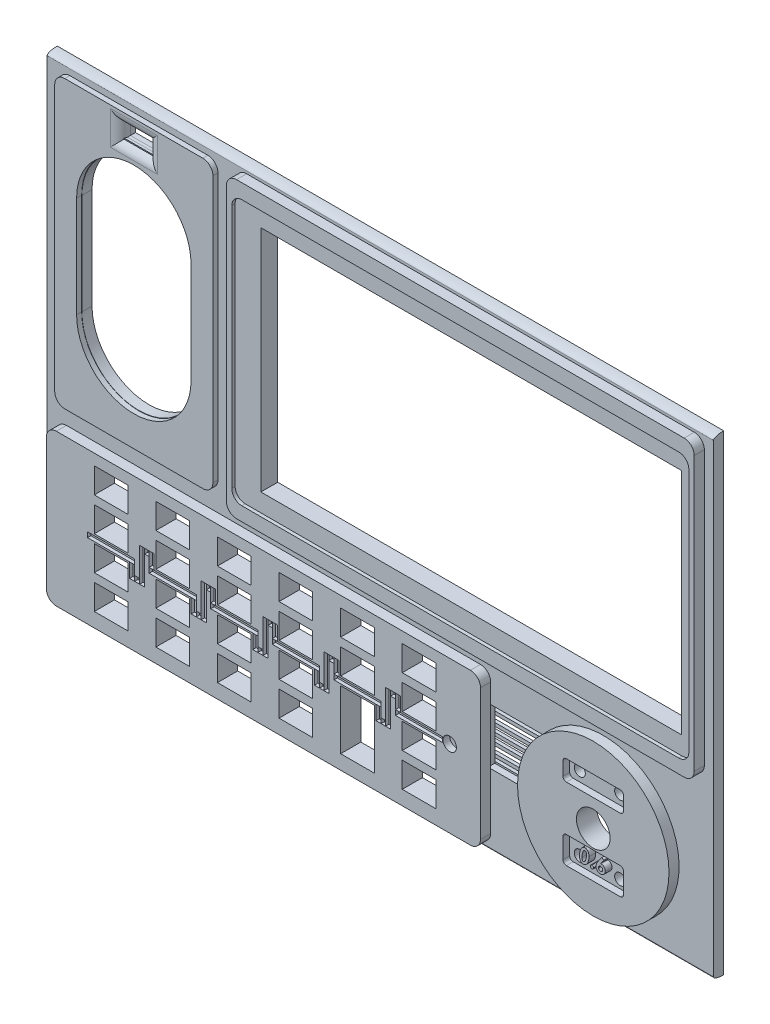
SolidWorks part; units mm, degrees
ref_plane "Front Plane" through (0, 0, 0) normal (0, 0, 1) x (1, 0, 0)
ref_plane "Top Plane" through (0, 0, 0) normal (0, 1, 0) x (1, 0, 0)
ref_plane "Right Plane" through (0, 0, 0) normal (1, 0, 0) x (0, 0, -1)
sketch "Sketch1" plane through (0, 0, 0) normal (0, 0, 1) x (1, 0, 0)
  line L1 (99, -70) -> (-99, -70)
  line L2 (99, -70) -> (99, 70)
  line L3 (99, 70) -> (-99, 70)
  line L4 (-99, -70) -> (-99, 70)
  line L5 (99, -70) -> (-99, 70) construction
  line L6 (99, 70) -> (-99, -70) construction
  point P0 (0, 0)
  dimension "D1" = 198
  dimension "D2" = 140
extrude "main_body" add sketch "Sketch1" along normal blind 3
fillet "long_corners" radius 3 2 edges at (0, 70, 3) (0, -70, 3) second distance 1 first distance on face at (0, 70, 1.5) first distance on face at (0, -70, 1.5)
sketch "Sketch2" plane through (0, 0, 3) normal (0, 0, 1) x (1, 0, 0)
  line L0 (-99, 24.75) -> (99, 24.75) construction
  line L1 (-99, 69) -> (-99, -69) construction
  line L2 (99, -69) -> (99, 69) construction
  line L3 (99, 69) -> (-99, 69) construction
  line L4 (-48.25, -17.75) -> (-95.25, -17.75)
  line L5 (-48.25, -17.75) -> (-48.25, 67.25)
  line L6 (-48.25, 67.25) -> (-95.25, 67.25)
  line L7 (-95.25, -17.75) -> (-95.25, 67.25)
  line L8 (-48.25, -17.75) -> (-95.25, 67.25) construction
  line L9 (-48.25, 67.25) -> (-95.25, -17.75) construction
  point P6 (-71.75, 24.75)
  dimension "D1" = 85
  dimension "D2" = 47
  dimension "D3" = 27.25
  dimension "D4" = 44.25
extrude "speaker" add sketch "Sketch2" along normal blind 1.5
fillet "speaker_corners" radius 3 4 edges at (-95.25, 67.25, 3.75) (-95.25, -17.75, 3.75) (-48.25, -17.75, 3.75) (-48.25, 67.25, 3.75)
sketch "Sketch19" plane through (0, 0, 4.5) normal (0, 0, 1) x (1, 0, 0)
  line L0 (-71.75, 67.25) -> (-71.75, -17.75) construction
  line L1 (-51.25, 67.25) -> (-92.25, 67.25) construction
  line L2 (-92.25, -17.75) -> (-51.25, -17.75) construction
  line L3 (-71.75, 8.25) -> (-71.75, 38.25) construction
  line L4 (-95.25, 64.25) -> (-95.25, -14.75) construction
  line L5 (-95.25, 24.75) -> (-48.25, 24.75) construction
  line L6 (-48.25, -14.75) -> (-48.25, 64.25) construction
  line L7 (-88.75, 8.25) -> (-88.75, 38.25)
  line L8 (-54.75, 8.25) -> (-54.75, 38.25)
  arc A0 (-88.75, 8.25) -> (-54.75, 8.25) centre (-71.75, 8.25) ccw
  arc A1 (-54.75, 38.25) -> (-88.75, 38.25) centre (-71.75, 38.25) ccw
  point P14 (-71.75, 23.25)
  point P19 (-71.75, -8.75)
  point P20 (-71.75, 55.25)
  dimension "D2" = 64
  dimension "D1" = 34
  dimension "D3" = 12
extrude "speaker_cut" cut sketch "Sketch19" against normal through all
sketch "Sketch21" plane through (0, 0, 0) normal (0, 0, -1) x (-1, 0, 0)
  line L0 (71.75, -8.75) -> (71.75, 55.25) construction
  line L2 (54.75, 8.25) -> (54.75, 38.25) construction
  line L3 (54.75, 23.25) -> (88.75, 23.25) construction
  line L4 (88.75, 38.25) -> (88.75, 8.25) construction
  line L5 (50.25, 59.25) -> (93.25, 59.25)
  line L6 (50.25, 59.25) -> (50.25, -12.75)
  line L7 (50.25, -12.75) -> (93.25, -12.75)
  line L8 (93.25, 59.25) -> (93.25, -12.75)
  line L9 (50.25, 59.25) -> (93.25, -12.75) construction
  line L10 (50.25, -12.75) -> (93.25, 59.25) construction
  arc A0 (54.75, 8.25) -> (88.75, 8.25) centre (71.75, 8.25) ccw construction
  arc A1 (88.75, 38.25) -> (54.75, 38.25) centre (71.75, 38.25) ccw construction
  point P14 (71.75, 23.25)
  dimension "D1" = 43
  dimension "D2" = 72
extrude "speaker_slot" cut sketch "Sketch21" against normal blind 3
sketch "Sketch36" plane through (0, 0, 3) normal (0, 0, -1) x (-1, 0, 0)
  line L0 (50.25, 23.25) -> (93.25, 23.25) construction
  line L1 (50.25, 59.25) -> (50.25, -12.75) construction
  line L2 (71.75, 8.2639) -> (71.75, 38.2361) construction
  line L3 (71.75, 8.2639) -> (71.75, 38.2361) construction
  line L4 (93.25, -12.75) -> (93.25, 59.25) construction
  line L5 (50.25, 59.25) -> (50.25, -12.75) construction
  line L6 (54.8316, 8.2639) -> (54.8316, 38.2361)
  line L9 (88.6684, 8.2639) -> (88.6684, 38.2361)
  line L10 (54.25, 8.2639) -> (54.25, 38.2361)
  line L11 (89.25, 8.2639) -> (89.25, 38.2361)
  line L12 (93.25, 59.25) -> (50.25, 59.25) construction
  line L13 (71.75, 59.25) -> (71.75, -12.75) construction
  line L14 (50.25, -12.75) -> (93.25, -12.75) construction
  line L23 (50.25, 57.25) -> (93.25, 57.25)
  line L25 (50.25, 57.25) -> (50.25, 56.75)
  line L26 (93.25, -0.25) -> (87.75, -0.25)
  line L27 (50.25, 56.75) -> (93.25, 56.75)
  line L28 (93.25, 57.25) -> (93.25, 56.75)
  line L37 (93.25, -12.75) -> (93.25, 59.25) construction
  line L38 (93.25, -0.25) -> (93.25, 0.25)
  line L39 (93.25, 0.25) -> (87.75, 0.25)
  line L48 (93.25, -10.75) -> (50.25, -10.75)
  line L49 (93.25, -10.75) -> (93.25, -10.25)
  line L50 (93.25, -10.25) -> (50.25, -10.25)
  line L51 (50.25, -10.75) -> (50.25, -10.25)
  line L52 (93.25, 46.75) -> (87.75, 46.75)
  line L53 (93.25, 46.75) -> (93.25, 46.25)
  line L54 (93.25, 46.25) -> (87.75, 46.25)
  line L55 (87.75, 46.75) -> (87.75, 46.25)
  line L56 (93.25, 35.25) -> (89.75, 35.25)
  line L57 (93.25, 35.25) -> (93.25, 34.75)
  line L58 (93.25, 34.75) -> (89.75, 34.75)
  line L59 (89.75, 35.25) -> (89.75, 34.75)
  line L60 (93.25, 23.25) -> (89.75, 23.25)
  line L61 (93.25, 23.25) -> (93.25, 23.75)
  line L62 (93.25, 23.75) -> (89.75, 23.75)
  line L63 (89.75, 23.25) -> (89.75, 23.75)
  line L64 (93.25, 10.75) -> (89.75, 10.75)
  line L65 (93.25, 10.75) -> (93.25, 11.25)
  line L66 (93.25, 11.25) -> (89.75, 11.25)
  line L67 (89.75, 10.75) -> (89.75, 11.25)
  line L68 (87.75, -0.25) -> (87.75, 0.25)
  line L69 (93.25, -5.25) -> (83.25, -5.25)
  line L70 (93.25, -5.25) -> (93.25, -5.75)
  line L71 (93.25, -5.75) -> (83.25, -5.75)
  line L72 (83.25, -5.25) -> (83.25, -5.75)
  line L73 (93.25, 52.25) -> (83.25, 52.25)
  line L74 (93.25, 52.25) -> (93.25, 51.75)
  line L75 (93.25, 51.75) -> (83.25, 51.75)
  line L76 (83.25, 52.25) -> (83.25, 51.75)
  line L77 (50.25, 52.25) -> (60.25, 52.25)
  line L78 (50.25, 52.25) -> (50.25, 51.75)
  line L79 (50.25, 51.75) -> (60.25, 51.75)
  line L80 (60.25, 52.25) -> (60.25, 51.75)
  line L81 (50.25, 46.75) -> (55.75, 46.75)
  line L82 (50.25, 46.75) -> (50.25, 46.25)
  line L83 (50.25, 46.25) -> (55.75, 46.25)
  line L84 (55.75, 46.75) -> (55.75, 46.25)
  line L85 (50.25, 35.25) -> (53.75, 35.25)
  line L86 (50.25, 35.25) -> (50.25, 34.75)
  line L87 (50.25, 34.75) -> (53.75, 34.75)
  line L88 (53.75, 35.25) -> (53.75, 34.75)
  line L89 (50.25, 23.25) -> (53.75, 23.25)
  line L90 (50.25, 23.25) -> (50.25, 23.75)
  line L91 (50.25, 23.75) -> (53.75, 23.75)
  line L92 (53.75, 23.25) -> (53.75, 23.75)
  line L93 (50.25, 10.25) -> (53.75, 10.25)
  line L94 (50.25, 10.25) -> (50.25, 10.75)
  line L95 (50.25, 10.75) -> (53.75, 10.75)
  line L96 (53.75, 10.25) -> (53.75, 10.75)
  line L97 (50.25, -0.25) -> (55.75, -0.25)
  line L98 (50.25, -0.25) -> (50.25, 0.25)
  line L99 (50.25, 0.25) -> (55.75, 0.25)
  line L100 (55.75, -0.25) -> (55.75, 0.25)
  line L101 (50.25, -5.25) -> (60.25, -5.25)
  line L102 (50.25, -5.25) -> (50.25, -5.75)
  line L103 (50.25, -5.75) -> (60.25, -5.75)
  line L104 (60.25, -5.25) -> (60.25, -5.75)
  arc A0 (54.25, 8.2639) -> (89.25, 8.2639) centre (71.75, 8.2639) ccw
  arc A1 (89.25, 38.2361) -> (54.25, 38.2361) centre (71.75, 38.2361) ccw
  arc A4 (54.8316, 8.2639) -> (88.6684, 8.2639) centre (71.75, 8.2639) ccw
  arc A5 (88.6684, 38.2361) -> (54.8316, 38.2361) centre (71.75, 38.2361) ccw
  point P6 (71.75, 23.25)
  point P22 (71.75, 23.25)
  point P31 (89.25, 23.25)
  point P32 (71.75, 55.1546)
  point P33 (71.75, -8.6546)
  point P95 (52, 35.25)
  point P96 (55.25, 51.75)
  point P97 (91.5, 10.75)
  dimension "D48" = 0.5816
  dimension "D1" = 33.8368
  dimension "D2" = 35
  dimension "D3" = 63.8091
  dimension "D4" = 0.5
  dimension "D5" = 0.5
  dimension "D6" = 0.5
  dimension "D7" = 0.5
  dimension "D8" = 0.5
  dimension "D9" = 11
  dimension "D10" = 11
  dimension "D11" = 5
  dimension "D12" = 4.5
  dimension "D13" = 10
  dimension "D14" = 5.5
  dimension "D15" = 3.5
  dimension "D16" = 3.5
  dimension "D17" = 0.5
  dimension "D18" = 0.5
  dimension "D19" = 0.5
  dimension "D20" = 0.5
  dimension "D21" = 11
  dimension "D22" = 11
  dimension "D23" = 5
  dimension "D24" = 10
  dimension "D25" = 5.5
  dimension "D26" = 3.5
  dimension "D27" = 3.5
  dimension "D28" = 0.5
  dimension "D29" = 0.5
  dimension "D30" = 0.5
  dimension "D31" = 0.5
  dimension "D32" = 0.5
  dimension "D33" = 0.5
  dimension "D34" = 0.5
  dimension "D35" = 12
  dimension "D36" = 10.5
  dimension "D37" = 5.5
  dimension "D38" = 5
  dimension "D39" = 4.5
  dimension "D40" = 3.5
  dimension "D41" = 10
  dimension "D42" = 4.5
  dimension "D43" = 5
  dimension "D44" = 10
  dimension "D45" = 3.5
  dimension "D46" = 5.5
  dimension "D47" = 10
extrude "speaker_print_support" add sketch "Sketch36" along normal blind 3
sketch "Sketch3" plane through (0, 0, 3) normal (0, 0, 1) x (1, 0, 0)
  line L0 (-99, 24.625) -> (99, 24.625) construction
  line L1 (-99, 69) -> (-99, -69) construction
  line L2 (99, -69) -> (99, 69) construction
  line L4 (-48.25, -14.75) -> (-48.25, 64.25) construction
  line L5 (96.25, -19) -> (-42.75, -19)
  line L6 (96.25, -19) -> (96.25, 68.25)
  line L7 (96.25, 68.25) -> (-42.75, 68.25)
  line L8 (-42.75, -19) -> (-42.75, 68.25)
  line L9 (96.25, -19) -> (-42.75, 68.25) construction
  line L10 (96.25, 68.25) -> (-42.75, -19) construction
  line L11 (99, 70) -> (-99, 70) construction
  point P8 (26.75, 24.625)
  dimension "D1" = 1.75
  dimension "D2" = 87.25
  dimension "D3" = 139
  dimension "D4" = 2.75
  dimension "D5" = 5.5
extrude "lcd" add sketch "Sketch3" along normal blind 3
fillet "lcd_corners" radius 3 4 edges at (96.25, -19, 4.5) (-42.75, -19, 4.5) (96.25, 68.25, 4.5) (-42.75, 68.25, 4.5)
sketch "Sketch9" plane through (0, 0, 6) normal (0, 0, 1) x (1, 0, 0)
  line L0 (-42.75, 24.5) -> (96.25, 24.5) construction
  line L1 (-42.75, 65.25) -> (-42.75, -16) construction
  line L2 (96.25, -16) -> (96.25, 65.25) construction
  line L3 (-39.75, -19) -> (93.25, -19) construction
  line L4 (94.65, -14.875) -> (-41.15, -14.875)
  line L5 (94.65, -14.875) -> (94.65, 63.875)
  line L6 (94.65, 63.875) -> (-41.15, 63.875)
  line L7 (-41.15, -14.875) -> (-41.15, 63.875)
  line L8 (94.65, -14.875) -> (-41.15, 63.875) construction
  line L9 (94.65, 63.875) -> (-41.15, -14.875) construction
  line L10 (93.25, 68.25) -> (-39.75, 68.25) construction
  line L11 (96.25, -16) -> (96.25, 65.25) construction
  point P6 (26.75, 24.5)
  dimension "D1" = 135.8
  dimension "D2" = 78.75
  dimension "D3" = 1.6
  dimension "D4" = 4.125
  dimension "D5" = 4.375
  dimension "D6" = 1.6
extrude "lcd_front" cut sketch "Sketch9" against normal blind 1
fillet "lcd_front_corners" radius 3 4 edges at (94.65, -14.875, 5.5) (94.65, 63.875, 5.5) (-41.15, 63.875, 5.5) (-41.15, -14.875, 5.5)
sketch "Sketch10" plane through (0, 0, 0) normal (0, 0, -1) x (-1, 0, 0)
  line L0 (-94.65, -11.875) -> (-94.65, 60.875) construction
  line L1 (-91.65, 63.875) -> (38.15, 63.875) construction
  line L2 (41.15, 63.875) -> (41.15, -14.875) construction
  line L3 (-94.65, 63.875) -> (41.15, 63.875) construction
  line L4 (33.5, -9.5) -> (-91.5, -9.5)
  line L5 (33.5, -9.5) -> (33.5, 58.5)
  line L6 (33.5, 58.5) -> (-91.5, 58.5)
  line L7 (-91.5, -9.5) -> (-91.5, 58.5)
  line L8 (-91.5, -9.5) -> (33.5, 58.5) construction
  line L9 (-91.5, 58.5) -> (33.5, -9.5) construction
  line L10 (-99, -70) -> (-99, 70) construction
  line L11 (-99, 70) -> (99, 70) construction
  line L13 (38.15, -14.875) -> (-91.65, -14.875) construction
  dimension "D1" = 125
  dimension "D2" = 68
  dimension "D3" = 7.5
  dimension "D4" = 7.65
  dimension "D5" = 11.5
  dimension "D6" = 5.375
  dimension "D7" = 3.15
  dimension "D8" = 5.375
  dimension "D9" = 5.375
extrude "lcd_back" cut sketch "Sketch10" against normal through all
sketch "Sketch4" plane through (0, 0, 3) normal (0, 0, 1) x (1, 0, 0)
  line L0 (-99, -45.75) -> (99, -45.75) construction
  line L1 (-99, 69) -> (-99, -69) construction
  line L2 (99, -69) -> (99, 69) construction
  line L4 (-92.25, -17.75) -> (-51.25, -17.75) construction
  line L5 (32.75, -68.25) -> (-96.25, -68.25)
  line L6 (32.75, -68.25) -> (32.75, -23.25)
  line L7 (32.75, -23.25) -> (-96.25, -23.25)
  line L8 (-96.25, -68.25) -> (-96.25, -23.25)
  line L9 (32.75, -68.25) -> (-96.25, -23.25) construction
  line L10 (32.75, -23.25) -> (-96.25, -68.25) construction
  line L11 (-99, -70) -> (99, -70) construction
  point P8 (-31.75, -45.75)
  dimension "D1" = 1.75
  dimension "D2" = 129
  dimension "D3" = 45
  dimension "D4" = 2.75
  dimension "D5" = 5.5
extrude "keypad" add sketch "Sketch4" along normal blind 3
fillet "keypad_corners" radius 3 4 edges at (-96.25, -68.25, 4.5) (32.75, -68.25, 4.5) (32.75, -23.25, 4.5) (-96.25, -23.25, 4.5)
sketch "Sketch25" plane through (0, 0, 6) normal (0, 0, 1) x (1, 0, 0)
  line L0 (-96.25, -30.25) -> (32.75, -30.25) construction
  line L1 (29.75, -23.25) -> (-93.25, -23.25) construction
  line L2 (-93.25, -68.25) -> (29.75, -68.25) construction
  line L3 (-77, -23.25) -> (-77, -68.25) construction
  line L5 (-35.4, -64) -> (32.75, -64) construction
  line L6 (-96.25, -26.25) -> (-96.25, -65.25) construction
  line L11 (32.75, -65.25) -> (32.75, -26.25) construction
  line L12 (-58.7, -23.25) -> (-58.7, -68.25) construction
  line L13 (-96.25, -40.25) -> (32.75, -40.25) construction
  line L14 (29.75, -23.25) -> (-93.25, -23.25) construction
  line L15 (-40.4, -23.25) -> (-40.4, -68.25) construction
  line L16 (-93.25, -68.25) -> (29.75, -68.25) construction
  line L17 (-72, -34) -> (-82, -34)
  line L18 (-22.1, -23.25) -> (-22.1, -68.25) construction
  line L19 (-96.25, -50.25) -> (32.75, -50.25) construction
  line L20 (-3.8, -23.25) -> (-3.8, -68.25) construction
  line L21 (-72, -34) -> (-72, -26.5)
  line L22 (14.5, -23.25) -> (14.5, -68.25) construction
  line L23 (-96.25, -26.25) -> (-96.25, -65.25) construction
  line L24 (-96.25, -60.25) -> (32.75, -60.25) construction
  line L25 (-72, -26.5) -> (-82, -26.5)
  line L26 (-82, -34) -> (-82, -26.5)
  line L27 (-72, -34) -> (-82, -26.5) construction
  line L28 (-72, -26.5) -> (-82, -34) construction
  line L29 (-72, -44) -> (-82, -44)
  line L30 (-72, -44) -> (-72, -36.5)
  line L31 (-72, -36.5) -> (-82, -36.5)
  line L32 (-82, -44) -> (-82, -36.5)
  line L33 (-72, -44) -> (-82, -36.5) construction
  line L34 (-72, -36.5) -> (-82, -44) construction
  line L35 (-72, -54) -> (-82, -54)
  line L36 (-72, -54) -> (-72, -46.5)
  line L37 (-72, -46.5) -> (-82, -46.5)
  line L38 (-82, -54) -> (-82, -46.5)
  line L39 (-72, -54) -> (-82, -46.5) construction
  line L40 (-72, -46.5) -> (-82, -54) construction
  line L41 (-72, -64) -> (-82, -64)
  line L42 (-72, -64) -> (-72, -56.5)
  line L43 (-72, -56.5) -> (-82, -56.5)
  line L44 (-82, -64) -> (-82, -56.5)
  line L45 (-72, -64) -> (-82, -56.5) construction
  line L46 (-72, -56.5) -> (-82, -64) construction
  line L47 (-53.7, -34) -> (-63.7, -34)
  line L48 (-53.7, -34) -> (-53.7, -26.5)
  line L49 (-53.7, -26.5) -> (-63.7, -26.5)
  line L50 (-63.7, -34) -> (-63.7, -26.5)
  line L51 (-53.7, -34) -> (-63.7, -26.5) construction
  line L52 (-53.7, -26.5) -> (-63.7, -34) construction
  line L53 (-53.7, -44) -> (-63.7, -44)
  line L54 (-53.7, -44) -> (-53.7, -36.5)
  line L55 (-53.7, -36.5) -> (-63.7, -36.5)
  line L56 (-63.7, -44) -> (-63.7, -36.5)
  line L57 (-53.7, -44) -> (-63.7, -36.5) construction
  line L58 (-53.7, -36.5) -> (-63.7, -44) construction
  line L59 (-53.7, -54) -> (-63.7, -54)
  line L60 (-53.7, -54) -> (-53.7, -46.5)
  line L61 (-53.7, -46.5) -> (-63.7, -46.5)
  line L62 (-63.7, -54) -> (-63.7, -46.5)
  line L63 (-53.7, -54) -> (-63.7, -46.5) construction
  line L64 (-53.7, -46.5) -> (-63.7, -54) construction
  line L65 (-53.7, -64) -> (-63.7, -64)
  line L66 (-53.7, -64) -> (-53.7, -56.5)
  line L67 (-53.7, -56.5) -> (-63.7, -56.5)
  line L68 (-63.7, -64) -> (-63.7, -56.5)
  line L69 (-53.7, -64) -> (-63.7, -56.5) construction
  line L70 (-53.7, -56.5) -> (-63.7, -64) construction
  line L71 (-35.4, -34) -> (-45.4, -34)
  line L72 (-35.4, -34) -> (-35.4, -26.5)
  line L73 (-35.4, -26.5) -> (-45.4, -26.5)
  line L74 (-45.4, -34) -> (-45.4, -26.5)
  line L75 (-35.4, -34) -> (-45.4, -26.5) construction
  line L76 (-35.4, -26.5) -> (-45.4, -34) construction
  line L77 (-35.4, -44) -> (-45.4, -44)
  line L78 (-35.4, -44) -> (-35.4, -36.5)
  line L79 (-35.4, -36.5) -> (-45.4, -36.5)
  line L80 (-45.4, -44) -> (-45.4, -36.5)
  line L81 (-35.4, -44) -> (-45.4, -36.5) construction
  line L82 (-35.4, -36.5) -> (-45.4, -44) construction
  line L83 (-35.4, -54) -> (-45.4, -54)
  line L84 (-35.4, -54) -> (-35.4, -46.5)
  line L85 (-35.4, -46.5) -> (-45.4, -46.5)
  line L86 (-45.4, -54) -> (-45.4, -46.5)
  line L87 (-35.4, -54) -> (-45.4, -46.5) construction
  line L88 (-35.4, -46.5) -> (-45.4, -54) construction
  line L89 (-35.4, -64) -> (-45.4, -64)
  line L90 (-35.4, -64) -> (-35.4, -56.5)
  line L91 (-35.4, -56.5) -> (-45.4, -56.5)
  line L92 (-45.4, -64) -> (-45.4, -56.5)
  line L93 (-35.4, -64) -> (-45.4, -56.5) construction
  line L94 (-35.4, -56.5) -> (-45.4, -64) construction
  line L95 (-17.1, -34) -> (-27.1, -34)
  line L96 (-17.1, -34) -> (-17.1, -26.5)
  line L97 (-17.1, -26.5) -> (-27.1, -26.5)
  line L98 (-27.1, -34) -> (-27.1, -26.5)
  line L99 (-17.1, -34) -> (-27.1, -26.5) construction
  line L100 (-17.1, -26.5) -> (-27.1, -34) construction
  line L101 (-17.1, -44) -> (-27.1, -44)
  line L102 (-17.1, -44) -> (-17.1, -36.5)
  line L103 (-17.1, -36.5) -> (-27.1, -36.5)
  line L104 (-27.1, -44) -> (-27.1, -36.5)
  line L105 (-17.1, -44) -> (-27.1, -36.5) construction
  line L106 (-17.1, -36.5) -> (-27.1, -44) construction
  line L111 (-17.1, -54) -> (-27.1, -54)
  line L112 (-17.1, -54) -> (-17.1, -46.5)
  line L113 (-17.1, -46.5) -> (-27.1, -46.5)
  line L114 (-27.1, -54) -> (-27.1, -46.5)
  line L115 (-17.1, -54) -> (-27.1, -46.5) construction
  line L116 (-17.1, -46.5) -> (-27.1, -54) construction
  line L117 (-17.1, -64) -> (-27.1, -64)
  line L118 (-17.1, -64) -> (-17.1, -56.5)
  line L119 (-17.1, -56.5) -> (-27.1, -56.5)
  line L120 (-27.1, -64) -> (-27.1, -56.5)
  line L121 (-17.1, -64) -> (-27.1, -56.5) construction
  line L122 (-17.1, -56.5) -> (-27.1, -64) construction
  line L127 (1.2, -34) -> (-8.8, -34)
  line L128 (1.2, -34) -> (1.2, -26.5)
  line L129 (1.2, -26.5) -> (-8.8, -26.5)
  line L130 (-8.8, -34) -> (-8.8, -26.5)
  line L131 (1.2, -34) -> (-8.8, -26.5) construction
  line L132 (1.2, -26.5) -> (-8.8, -34) construction
  line L133 (19.5, -34) -> (9.5, -34)
  line L134 (19.5, -34) -> (19.5, -26.5)
  line L135 (19.5, -26.5) -> (9.5, -26.5)
  line L136 (9.5, -34) -> (9.5, -26.5)
  line L137 (19.5, -34) -> (9.5, -26.5) construction
  line L138 (19.5, -26.5) -> (9.5, -34) construction
  line L139 (1.2, -44) -> (-8.8, -44)
  line L140 (1.2, -44) -> (1.2, -36.5)
  line L141 (1.2, -36.5) -> (-8.8, -36.5)
  line L142 (-8.8, -44) -> (-8.8, -36.5)
  line L143 (1.2, -44) -> (-8.8, -36.5) construction
  line L144 (1.2, -36.5) -> (-8.8, -44) construction
  line L145 (19.5, -44) -> (9.5, -44)
  line L146 (19.5, -44) -> (19.5, -36.5)
  line L147 (19.5, -36.5) -> (9.5, -36.5)
  line L148 (9.5, -44) -> (9.5, -36.5)
  line L149 (19.5, -44) -> (9.5, -36.5) construction
  line L150 (19.5, -36.5) -> (9.5, -44) construction
  line L151 (19.5, -54) -> (9.5, -54)
  line L152 (19.5, -54) -> (19.5, -46.5)
  line L153 (19.5, -46.5) -> (9.5, -46.5)
  line L154 (9.5, -54) -> (9.5, -46.5)
  line L155 (19.5, -54) -> (9.5, -46.5) construction
  line L156 (19.5, -46.5) -> (9.5, -54) construction
  line L157 (19.5, -64) -> (9.5, -64)
  line L158 (19.5, -64) -> (19.5, -56.5)
  line L159 (19.5, -56.5) -> (9.5, -56.5)
  line L160 (9.5, -64) -> (9.5, -56.5)
  line L161 (19.5, -64) -> (9.5, -56.5) construction
  line L162 (19.5, -56.5) -> (9.5, -64) construction
  line L163 (1.2, -64) -> (-8.8, -64)
  line L164 (1.2, -64) -> (1.2, -46.5)
  line L165 (1.2, -46.5) -> (-8.8, -46.5)
  line L166 (-8.8, -64) -> (-8.8, -46.5)
  line L167 (1.2, -64) -> (-8.8, -46.5) construction
  line L168 (1.2, -46.5) -> (-8.8, -64) construction
  point P34 (-77, -30.25)
  point P39 (-77, -40.25)
  point P44 (-77, -50.25)
  point P49 (-77, -60.25)
  point P54 (-58.7, -30.25)
  point P59 (-58.7, -40.25)
  point P64 (-58.7, -50.25)
  point P69 (-58.7, -60.25)
  point P74 (-40.4, -30.25)
  point P79 (-40.4, -40.25)
  point P84 (-40.4, -50.25)
  point P89 (-40.4, -60.25)
  point P94 (-22.1, -30.25)
  point P99 (-22.1, -40.25)
  point P104 (-22.1, -50.25)
  point P109 (-22.1, -60.25)
  point P114 (-3.8, -30.25)
  point P119 (14.5, -30.25)
  point P124 (-3.8, -40.25)
  point P129 (14.5, -40.25)
  point P134 (14.5, -50.25)
  point P139 (14.5, -60.25)
  point P144 (-3.8, -55.25)
  dimension "D1" = 18.25
  dimension "D2" = 18.3
  dimension "D3" = 18.3
  dimension "D4" = 18.3
  dimension "D5" = 18.3
  dimension "D6" = 18.3
  dimension "D7" = 19.25
  dimension "D8" = 7
  dimension "D9" = 10
  dimension "D10" = 10
  dimension "D11" = 10
  dimension "D12" = 8
  dimension "D13" = 10
  dimension "D14" = 10
  dimension "D15" = 10
  dimension "D16" = 10
  dimension "D17" = 10
  dimension "D18" = 10
  dimension "D19" = 10
  dimension "D20" = 10
  dimension "D21" = 10
  dimension "D22" = 10
  dimension "D23" = 10
  dimension "D24" = 10
  dimension "D25" = 10
  dimension "D26" = 10
  dimension "D27" = 10
  dimension "D28" = 10
  dimension "D29" = 10
  dimension "D30" = 10
  dimension "D31" = 10
  dimension "D32" = 10
  dimension "D33" = 10
  dimension "D34" = 10
  dimension "D35" = 10
  dimension "D36" = 7.5
  dimension "D37" = 7.5
  dimension "D38" = 7.5
  dimension "D39" = 7.5
  dimension "D40" = 7.5
  dimension "D41" = 7.5
  dimension "D42" = 17.5
  dimension "D43" = 7.5
  dimension "D44" = 7.5
  dimension "D45" = 7.5
  dimension "D46" = 7.5
  dimension "D47" = 7.5
  dimension "D48" = 7.5
  dimension "D49" = 7.5
  dimension "D50" = 7.5
  dimension "D51" = 7.5
  dimension "D52" = 7.5
  dimension "D53" = 7.5
  dimension "D54" = 7.5
  dimension "D55" = 7.5
  dimension "D56" = 7.5
  dimension "D57" = 7.5
  dimension "D58" = 7.5
  dimension "D59" = 5
extrude "keypad_cuts_0.8" cut sketch "Sketch25" against normal through all
sketch "Sketch40" plane through (0, 0, 6) normal (0, 0, 1) x (1, 0, 0)
  line L0 (16.75, -23.25) -> (16.75, -68.25) construction
  line L1 (-8.25, -23.25) -> (-8.25, -68.25) construction
  line L2 (-67.25, -23.25) -> (-67.25, -68.25) construction
  line L3 (-96.25, -45.75) -> (32.75, -45.75) construction
  line L4 (-83.25, -23.25) -> (-83.25, -68.25) construction
  line L5 (29.75, -23.25) -> (-93.25, -23.25) construction
  line L6 (-93.25, -68.25) -> (29.75, -68.25) construction
  line L11 (-77.25, -49.75) -> (-89.25, -49.75)
  line L12 (-77.25, -49.75) -> (-77.25, -41.75)
  line L13 (-93.25, -68.25) -> (29.75, -68.25) construction
  line L14 (-77.25, -41.75) -> (-89.25, -41.75)
  line L15 (-89.25, -49.75) -> (-89.25, -41.75)
  line L16 (-35.25, -68.25) -> (-35.25, -23.25) construction
  line L18 (29.75, -23.25) -> (-93.25, -23.25) construction
  line L19 (-77.25, -49.75) -> (-89.25, -41.75) construction
  line L20 (-51.25, -68.25) -> (-51.25, -23.25) construction
  line L22 (-77.25, -41.75) -> (-89.25, -49.75) construction
  line L23 (-61.25, -49.75) -> (-73.25, -49.75)
  line L24 (-61.25, -49.75) -> (-61.25, -41.75)
  line L25 (-61.25, -41.75) -> (-73.25, -41.75)
  line L26 (-73.25, -49.75) -> (-73.25, -41.75)
  line L27 (-61.25, -49.75) -> (-73.25, -41.75) construction
  line L28 (-61.25, -41.75) -> (-73.25, -49.75) construction
  line L29 (-45.25, -49.75) -> (-57.25, -49.75)
  line L30 (-45.25, -49.75) -> (-45.25, -41.75)
  line L31 (-45.25, -41.75) -> (-57.25, -41.75)
  line L32 (-57.25, -49.75) -> (-57.25, -41.75)
  line L33 (-45.25, -49.75) -> (-57.25, -41.75) construction
  line L34 (-45.25, -41.75) -> (-57.25, -49.75) construction
  line L35 (-29.25, -49.75) -> (-41.25, -49.75)
  line L36 (-29.25, -49.75) -> (-29.25, -41.75)
  line L37 (-29.25, -41.75) -> (-41.25, -41.75)
  line L38 (-41.25, -49.75) -> (-41.25, -41.75)
  line L39 (-29.25, -49.75) -> (-41.25, -41.75) construction
  line L40 (-29.25, -41.75) -> (-41.25, -49.75) construction
  line L45 (-2.25, -41.75) -> (-14.25, -41.75)
  line L46 (-2.25, -41.75) -> (-2.25, -33.75)
  line L51 (-2.25, -33.75) -> (-14.25, -33.75)
  line L52 (-14.25, -41.75) -> (-14.25, -33.75)
  line L53 (22.75, -35.75) -> (10.75, -35.75)
  line L54 (22.75, -35.75) -> (22.75, -27.75)
  line L55 (22.75, -27.75) -> (10.75, -27.75)
  line L56 (10.75, -35.75) -> (10.75, -27.75)
  line L57 (22.75, -35.75) -> (10.75, -27.75) construction
  line L58 (22.75, -27.75) -> (10.75, -35.75) construction
  line L59 (22.75, -63.75) -> (10.75, -63.75)
  line L60 (22.75, -63.75) -> (22.75, -55.75)
  line L61 (22.75, -55.75) -> (10.75, -55.75)
  line L62 (10.75, -63.75) -> (10.75, -55.75)
  line L63 (22.75, -63.75) -> (10.75, -55.75) construction
  line L64 (22.75, -55.75) -> (10.75, -63.75) construction
  line L69 (32.75, -65.25) -> (32.75, -26.25) construction
  line L70 (-2.25, -57.25) -> (-14.25, -57.25)
  line L75 (-2.25, -57.25) -> (-2.25, -49.25)
  line L76 (-2.25, -49.25) -> (-14.25, -49.25)
  line L77 (-2.25, -41.75) -> (-14.25, -33.75) construction
  line L78 (-2.25, -33.75) -> (-14.25, -41.75) construction
  line L85 (-14.25, -57.25) -> (-14.25, -49.25)
  line L86 (-2.25, -57.25) -> (-14.25, -49.25) construction
  line L87 (-2.25, -49.25) -> (-14.25, -57.25) construction
  line L88 (-96.25, -26.25) -> (-96.25, -65.25) construction
  line L89 (32.75, -65.25) -> (32.75, -26.25) construction
  line L93 (32.75, -59.75) -> (-96.25, -59.75) construction
  line L94 (-96.25, -31.75) -> (32.75, -31.75) construction
  line L95 (32.75, -31.75) -> (32.75, -37.75) construction
  line L96 (32.75, -37.75) -> (-96.25, -37.75) construction
  line L99 (-96.25, -26.25) -> (-96.25, -65.25) construction
  line L100 (-96.25, -53.75) -> (32.75, -53.75) construction
  point P18 (-83.25, -45.75)
  point P25 (-67.25, -45.75)
  point P30 (-51.25, -45.75)
  point P35 (-35.25, -45.75)
  point P40 (-8.25, -37.75)
  point P45 (-8.25, -53.25)
  point P50 (16.75, -31.75)
  point P55 (16.75, -59.75)
  dimension "D1" = 8
  dimension "D2" = 8
  dimension "D3" = 8
  dimension "D4" = 8
  dimension "D5" = 8
  dimension "D6" = 12
  dimension "D7" = 8
  dimension "D8" = 8
  dimension "D9" = 12
  dimension "D10" = 12
  dimension "D11" = 12
  dimension "D12" = 12
  dimension "D13" = 12
  dimension "D14" = 12
  dimension "D15" = 8
  dimension "D16" = 12
  dimension "D17" = 8
  dimension "D18" = 8
  dimension "D19" = 27
  dimension "D20" = 14
  dimension "D21" = 16
  dimension "D22" = 16
  dimension "D23" = 16
  dimension "D24" = 25
  dimension "D25" = 14
extrude "keypad_cuts_0.7" [suppressed] cut sketch "Sketch40" against normal through all
sketch "Sketch41" [suppressed] plane through (0, 0, 0) normal (0, 0, -1) x (-1, 0, 0)
  line L0 (-22.75, -27.75) -> (-10.75, -35.75) construction
  line L1 (-22.75, -55.75) -> (-10.75, -63.75) construction
  line L2 (8.25, -33.75) -> (8.25, -57.25) construction
  line L3 (-10.75, -63.75) -> (-22.75, -63.75) construction
  line L4 (29.25, -45.75) -> (89.25, -45.75) construction
  line L5 (29.25, -49.75) -> (29.25, -41.75) construction
  line L6 (89.25, -41.75) -> (89.25, -49.75) construction
  line L7 (-6.75, -39.75) -> (-26.75, -39.75)
  line L8 (2.25, -33.75) -> (14.25, -33.75) construction
  line L9 (-6.75, -39.75) -> (-6.75, -23.75)
  line L10 (91.25, -52.75) -> (27.25, -52.75)
  line L11 (-6.75, -23.75) -> (-26.75, -23.75)
  line L12 (14.25, -57.25) -> (2.25, -57.25) construction
  line L13 (-26.75, -39.75) -> (-26.75, -23.75)
  line L14 (-10.75, -55.75) -> (-22.75, -63.75) construction
  line L15 (-6.75, -39.75) -> (-26.75, -23.75) construction
  line L16 (-10.75, -35.75) -> (-22.75, -35.75) construction
  line L17 (-22.75, -35.75) -> (-22.75, -27.75) construction
  line L18 (-22.75, -35.75) -> (-10.75, -27.75) construction
  line L19 (-6.75, -23.75) -> (-26.75, -39.75) construction
  line L21 (-6.75, -67.75) -> (-26.75, -67.75)
  line L22 (16.25, -59.5) -> (0.25, -59.5)
  line L23 (-6.75, -67.75) -> (-6.75, -51.75)
  line L24 (91.25, -52.75) -> (91.25, -38.75)
  line L25 (-6.75, -51.75) -> (-26.75, -51.75)
  line L26 (91.25, -38.75) -> (27.25, -38.75)
  line L27 (-26.75, -67.75) -> (-26.75, -51.75)
  line L28 (27.25, -52.75) -> (27.25, -38.75)
  line L29 (-6.75, -67.75) -> (-26.75, -51.75) construction
  line L30 (91.25, -52.75) -> (27.25, -38.75) construction
  line L31 (-6.75, -51.75) -> (-26.75, -67.75) construction
  line L36 (16.25, -59.5) -> (16.25, -31.5)
  line L37 (16.25, -31.5) -> (0.25, -31.5)
  line L42 (0.25, -59.5) -> (0.25, -31.5)
  line L43 (16.25, -59.5) -> (0.25, -31.5) construction
  line L48 (91.25, -38.75) -> (27.25, -52.75) construction
  line L49 (16.25, -31.5) -> (0.25, -59.5) construction
  point P19 (59.25, -45.75)
  point P44 (8.25, -45.5)
  point P68 (-16.75, -59.75)
  point P69 (-16.75, -31.75)
  dimension "D1" = 20
  dimension "D2" = 20
  dimension "D3" = 16
  dimension "D4" = 16
  dimension "D5" = 16
  dimension "D6" = 28
  dimension "D7" = 64
  dimension "D8" = 14
extrude "keypad_back_0.7" [suppressed] cut sketch "Sketch41" against normal blind 5
sketch "Sketch5" plane through (0, 0, 3) normal (0, 0, 1) x (1, 0, 0)
  line L0 (32.75, -45.75) -> (99, -45.75) construction
  line L1 (32.75, -65.25) -> (32.75, -26.25) construction
  line L2 (99, -69) -> (99, 69) construction
  circle A0 centre (66.25, -45.75) radius 22.5
  dimension "D1" = 45
  dimension "D2" = 32.75
  dimension "D3" = 33.5
extrude "vfo" add sketch "Sketch5" along normal blind 3
sketch "Sketch7" plane through (0, 0, 6) normal (0, 0, 1) x (1, 0, 0)
  line L0 (43.75, -45.75) -> (88.75, -45.75) construction
  line L1 (66.25, -23.25) -> (66.25, -68.25) construction
  circle A0 centre (66.25, -45.75) radius 22.5 construction
  circle A1 centre (66.25, -45.75) radius 22.5 construction
  circle A2 centre (66.25, -45.75) radius 5
  dimension "D1" = 10
extrude "vfo_encoder_knob_cut" cut sketch "Sketch7" against normal through all
sketch "Sketch37" plane through (0, 0, 6) normal (0, 0, 1) x (1, 0, 0)
  line L1 (57.25, -51.25) -> (75.25, -51.25)
  line L2 (57.25, -51.25) -> (57.25, -59.25)
  line L3 (57.25, -59.25) -> (75.25, -59.25)
  line L4 (75.25, -51.25) -> (75.25, -59.25)
  line L5 (57.25, -31.75) -> (75.25, -31.75)
  line L6 (57.25, -31.75) -> (57.25, -37.75)
  line L7 (57.25, -37.75) -> (75.25, -37.75)
  line L8 (75.25, -31.75) -> (75.25, -37.75)
  circle A0 centre (66.25, -45.75) radius 5 construction
  dimension "D1" = 8
  dimension "D2" = 18
  dimension "D3" = 5.5
  dimension "D4" = 9
  dimension "D5" = 18
  dimension "D6" = 6
  dimension "D7" = 8
  dimension "D8" = 9
extrude "logo_cut" cut sketch "Sketch37" against normal blind 2
sketch "Sketch44" plane through (0, 0, 6) normal (0, 0, 1) x (1, 0, 0)
  line L0 (66.25, -23.25) -> (66.25, -68.25) construction
  line L3 (43.75, -45.75) -> (88.75, -45.75) construction
  line L6 (66.25, -34.75) -> (72.25, -34.75) construction
  line L7 (66.25, -56.75) -> (72.25, -56.75) construction
  line L9 (60.25, -34.75) -> (66.25, -34.75) construction
  line L11 (60.25, -56.75) -> (66.25, -56.75) construction
  circle A0 centre (66.25, -45.75) radius 22.5 construction
  circle A1 centre (66.25, -45.75) radius 22.5 construction
  circle A4 centre (60.25, -34.75) radius 1.65
  circle A5 centre (72.25, -34.75) radius 1.65
  circle A6 centre (60.25, -56.75) radius 1.65
  circle A7 centre (72.25, -56.75) radius 1.65
  point P8 (72.3516, -34.75)
  point P9 (60.3294, -34.75)
  point P10 (60.1228, -56.75)
  point P11 (72.3384, -56.75)
  dimension "D9" = 3.3
  dimension "D10" = 3.3
  dimension "D11" = 3.3
  dimension "D12" = 3.3
  dimension "D7" = 11
  dimension "D8" = 11
  dimension "D13" = 6
  dimension "D14" = 6
  dimension "D15" = 6
  dimension "D16" = 6
extrude "encoder_mount_holes" cut sketch "Sketch44" against normal through all
fillet "enc_cut_corners" radius 1 8 edges at (57.25, -59.25, 5) (75.25, -59.25, 5) (75.25, -51.25, 5) (57.25, -51.25, 5) (57.25, -37.75, 5) (75.25, -37.75, 5) (75.25, -31.75, 5) (57.25, -31.75, 5)
sketch "Sketch39" plane through (0, 0, 4) normal (0, 0, 1) x (1, 0, 0)
  line L0 (57.25, -52.25) -> (57.25, -58.25) construction
  line L1 (58.25, -59.25) -> (74.25, -59.25) construction
  text T0 "0.6" font "Century Gothic" height in points 16
  point P5 (0, 0)
  point P6 (0, 0)
  dimension "D1" = 4.75
  dimension "D2" = 3
extrude "logo_txt_ver" add sketch "Sketch39" along normal blind 2
sketch "esp32" plane through (0, 0, 0) normal (0, 0, -1) x (-1, 0, 0)
  line L0 (99, -70) -> (-99, -70) construction
  line L1 (-50.5, -32.05) -> (-32, -32.05)
  line L2 (-50.5, -32.05) -> (-50.5, -48.55)
  line L3 (-50.5, -48.55) -> (-32, -48.55)
  line L4 (-32, -32.05) -> (-32, -48.55)
  line L5 (-99, -70) -> (-99, 70) construction
  dimension "D1" = 21.45
  dimension "D2" = 48.5
  dimension "D3" = 16.5
  dimension "D4" = 18.5
extrude "esp32_can_cut" cut sketch "esp32" against normal blind 3
sketch "Sketch43" plane through (0, 0, 0) normal (0, 0, -1) x (-1, 0, 0)
  line L0 (99, -70) -> (-99, -70) construction
  line L1 (-34, -50.5) -> (-50.5, -50.5)
  line L2 (-34, -50.5) -> (-34, -67)
  line L3 (-34, -67) -> (-50.5, -67)
  line L4 (-50.5, -50.5) -> (-50.5, -67)
  line L5 (-99, -70) -> (-99, 70) construction
  dimension "D1" = 16.5
  dimension "D2" = 16.5
  dimension "D3" = 3
  dimension "D4" = 48.5
extrude "lora_cut" cut sketch "Sketch43" against normal blind 2.5
fillet "rf_corners" [suppressed] radius 1
sketch "Sketch47" plane through (0, 0, 0) normal (0, 0, -1) x (-1, 0, 0)
  line L0 (-50.5, -48.55) -> (-32, -48.55) construction
  line L1 (-31, -49.55) -> (-58, -49.55)
  line L2 (-31, -49.55) -> (-31, -31.05)
  line L3 (-31, -31.05) -> (-58, -31.05)
  line L4 (-58, -49.55) -> (-58, -31.05)
  line L5 (-31, -49.55) -> (-58, -31.05) construction
  line L6 (-31, -31.05) -> (-58, -49.55) construction
  line L7 (-50.5, -32.05) -> (-50.5, -48.55) construction
  point P0 (-44.5, -40.3)
  dimension "D1" = 27
  dimension "D2" = 18.5
  dimension "D3" = 1
  dimension "D4" = 7.5
extrude "esp32_ex_cut" cut sketch "Sketch47" against normal blind 1
sketch "Sketch49" plane through (0, 0, 0) normal (0, 0, -1) x (-1, 0, 0)
  line L0 (71.75, 59.25) -> (71.75, 70) construction
  line L1 (93.25, 59.25) -> (50.25, 59.25) construction
  line L2 (-99, 70) -> (99, 70) construction
  line L4 (75.75, 59.35) -> (67.75, 59.35)
  line L5 (75.75, 59.35) -> (75.75, 63.35)
  line L6 (75.75, 63.35) -> (67.75, 63.35)
  line L7 (67.75, 59.35) -> (67.75, 63.35)
  line L8 (75.75, 59.35) -> (67.75, 63.35) construction
  line L9 (75.75, 63.35) -> (67.75, 59.35) construction
  point P6 (71.75, 61.35)
  dimension "D1" = 8
  dimension "D2" = 4
  dimension "D3" = 0.1
extrude "amb_sensor" cut sketch "Sketch49" against normal through all
fillet "amb_corners" radius 3 4 edges at (-67.75, 61.35, 4.5) (-71.75, 63.35, 4.5) (-75.75, 61.35, 4.5) (-71.75, 59.35, 4.5)
sketch "Sketch50" plane through (0, 0, 6) normal (0, 0, 1) x (1, 0, 0)
  line L0 (-96.25, -45.1902) -> (-96.25, -45.25) construction
  line L1 (-96.25, -26.25) -> (-96.25, -65.25) construction
  line L2 (-96.25, -40.25) -> (32.75, -40.25) construction
  line L3 (-67.75, -23.25) -> (-67.75, -68.25) construction
  line L4 (29.75, -23.25) -> (-93.25, -23.25) construction
  line L5 (-93.25, -68.25) -> (29.75, -68.25) construction
  line L6 (-31.25, -23.25) -> (-31.25, -68.25) construction
  line L7 (29.75, -23.25) -> (-93.25, -23.25) construction
  line L8 (-49.5, -23.25) -> (-49.5, -68.25) construction
  line L9 (5.25, -23.25) -> (5.25, -68.25) construction
  line L10 (-13, -23.25) -> (-13, -68.25) construction
  line L11 (-96.25, -26.25) -> (-96.25, -65.25) construction
  line L12 (-96.25, -45.25) -> (32.75, -45.25) construction
  line L13 (32.75, -65.25) -> (32.75, -26.25) construction
  line L14 (9.5, -36.5) -> (9.5, -44) construction
  line L15 (-70, -46) -> (-84, -46)
  line L16 (-70, -46) -> (-70, -44.5)
  line L17 (-70, -44.5) -> (-84, -44.5)
  line L18 (-84, -46) -> (-84, -44.5)
  line L19 (-70, -46) -> (-84, -44.5) construction
  line L20 (-70, -44.5) -> (-84, -46) construction
  line L21 (-51.7, -46) -> (-65.7, -46)
  line L22 (-51.7, -46) -> (-51.7, -44.5)
  line L23 (-51.7, -44.5) -> (-65.7, -44.5)
  line L24 (-65.7, -46) -> (-65.7, -44.5)
  line L25 (-51.7, -46) -> (-65.7, -44.5) construction
  line L26 (-51.7, -44.5) -> (-65.7, -46) construction
  line L27 (-33.4, -46) -> (-47.4, -46)
  line L28 (-33.4, -46) -> (-33.4, -44.5)
  line L29 (-33.4, -44.5) -> (-47.4, -44.5)
  line L30 (-47.4, -46) -> (-47.4, -44.5)
  line L31 (-33.4, -46) -> (-47.4, -44.5) construction
  line L32 (-33.4, -44.5) -> (-47.4, -46) construction
  line L33 (-15.1, -46) -> (-29.1, -46)
  line L34 (-15.1, -46) -> (-15.1, -44.5)
  line L35 (-15.1, -44.5) -> (-29.1, -44.5)
  line L36 (-29.1, -46) -> (-29.1, -44.5)
  line L37 (-15.1, -46) -> (-29.1, -44.5) construction
  line L38 (-15.1, -44.5) -> (-29.1, -46) construction
  line L39 (3.2, -46) -> (-10.8, -46)
  line L40 (3.2, -46) -> (3.2, -44.5)
  line L41 (3.2, -44.5) -> (-10.8, -44.5)
  line L42 (-10.8, -46) -> (-10.8, -44.5)
  line L43 (3.2, -46) -> (-10.8, -44.5) construction
  line L44 (3.2, -44.5) -> (-10.8, -46) construction
  line L45 (21.5, -46) -> (7.5, -46)
  line L46 (21.5, -46) -> (21.5, -44.5)
  line L47 (21.5, -44.5) -> (7.5, -44.5)
  line L48 (7.5, -46) -> (7.5, -44.5)
  line L49 (21.5, -46) -> (7.5, -44.5) construction
  line L50 (21.5, -44.5) -> (7.5, -46) construction
  line L51 (-8.8, -36.5) -> (-8.8, -44) construction
  line L52 (-27.1, -36.5) -> (-27.1, -44) construction
  line L53 (-45.4, -36.5) -> (-45.4, -44) construction
  line L54 (-63.7, -36.5) -> (-63.7, -44) construction
  line L55 (-82, -36.5) -> (-82, -44) construction
  line L56 (1.2, -64) -> (1.2, -46.5) construction
  line L57 (7.49, -40.25) -> (8.99, -40.25)
  line L58 (32.75, -65.25) -> (32.75, -48.55) construction
  line L59 (32.75, -50.25) -> (-96.25, -50.25) construction
  line L60 (7.49, -40.25) -> (7.49, -44.49)
  line L61 (7.49, -44.49) -> (8.99, -44.49)
  line L62 (8.99, -40.25) -> (8.99, -44.49)
  line L63 (3.2, -50.25) -> (1.7, -50.25)
  line L64 (3.2, -50.25) -> (3.2, -46.01)
  line L65 (3.2, -46.01) -> (1.7, -46.01)
  line L66 (1.7, -50.25) -> (1.7, -46.01)
  line L67 (4.52, -40.25) -> (6.02, -40.25)
  line L68 (4.52, -40.25) -> (4.52, -50.25)
  line L69 (4.52, -50.25) -> (6.02, -50.25)
  line L70 (6.02, -40.25) -> (6.02, -50.25)
  line L71 (3.21, -50.25) -> (4.51, -50.25)
  line L72 (3.21, -50.25) -> (3.21, -48.75)
  line L73 (3.21, -48.75) -> (4.51, -48.75)
  line L74 (4.51, -50.25) -> (4.51, -48.75)
  line L75 (6.03, -40.25) -> (7.48, -40.25)
  line L76 (6.03, -40.25) -> (6.03, -41.75)
  line L77 (6.03, -41.75) -> (7.48, -41.75)
  line L78 (7.48, -40.25) -> (7.48, -41.75)
  line L79 (-72, -54) -> (-72, -46.5) construction
  line L80 (-13.78, -40.25) -> (-12.28, -40.25)
  line L81 (-13.78, -40.25) -> (-13.78, -50.25)
  line L82 (-13.78, -50.25) -> (-12.28, -50.25)
  line L83 (-12.28, -40.25) -> (-12.28, -50.25)
  line L84 (-31.88, -40.25) -> (-30.38, -40.25)
  line L85 (-31.88, -40.25) -> (-31.88, -50.25)
  line L86 (-31.88, -50.25) -> (-30.38, -50.25)
  line L87 (-30.38, -40.25) -> (-30.38, -50.25)
  line L88 (-50.23, -40.25) -> (-48.73, -40.25)
  line L89 (-50.23, -40.25) -> (-50.23, -50.25)
  line L90 (-50.23, -50.25) -> (-48.73, -50.25)
  line L91 (-48.73, -40.25) -> (-48.73, -50.25)
  line L92 (-68.53, -40.25) -> (-67.03, -40.25)
  line L93 (-68.53, -40.25) -> (-68.53, -50.25)
  line L94 (-68.53, -50.25) -> (-67.03, -50.25)
  line L95 (-67.03, -40.25) -> (-67.03, -50.25)
  line L96 (-70, -46.01) -> (-71.5, -46.01)
  line L97 (-70, -46.01) -> (-70, -50.25)
  line L98 (-70, -50.25) -> (-71.5, -50.25)
  line L99 (-71.5, -46.01) -> (-71.5, -50.25)
  line L100 (-69.99, -50.25) -> (-68.54, -50.25)
  line L101 (-69.99, -50.25) -> (-69.99, -48.75)
  line L102 (-69.99, -48.75) -> (-68.54, -48.75)
  line L103 (-68.54, -50.25) -> (-68.54, -48.75)
  line L104 (-53.7, -54) -> (-53.7, -46.5) construction
  line L105 (-67.02, -40.25) -> (-65.72, -40.25)
  line L106 (-67.02, -40.25) -> (-67.02, -41.75)
  line L107 (-67.02, -41.75) -> (-65.72, -41.75)
  line L108 (-65.72, -40.25) -> (-65.72, -41.75)
  line L109 (-65.71, -40.25) -> (-64.21, -40.25)
  line L110 (-65.71, -40.25) -> (-65.71, -44.49)
  line L111 (-65.71, -44.49) -> (-64.21, -44.49)
  line L112 (-64.21, -40.25) -> (-64.21, -44.49)
  line L113 (-51.7, -46.01) -> (-53.2, -46.01)
  line L114 (-51.7, -46.01) -> (-51.7, -50.25)
  line L115 (-51.7, -50.25) -> (-53.2, -50.25)
  line L116 (-53.2, -46.01) -> (-53.2, -50.25)
  line L117 (-51.69, -50.25) -> (-50.24, -50.25)
  line L118 (-51.69, -50.25) -> (-51.69, -48.75)
  line L119 (-51.69, -48.75) -> (-50.24, -48.75)
  line L120 (-50.24, -50.25) -> (-50.24, -48.75)
  line L121 (-48.72, -40.25) -> (-47.42, -40.25)
  line L122 (-48.72, -40.25) -> (-48.72, -41.75)
  line L123 (-48.72, -41.75) -> (-47.42, -41.75)
  line L124 (-47.42, -40.25) -> (-47.42, -41.75)
  line L125 (-47.41, -40.25) -> (-45.91, -40.25)
  line L126 (-47.41, -40.25) -> (-47.41, -44.49)
  line L127 (-47.41, -44.49) -> (-45.91, -44.49)
  line L128 (-45.91, -40.25) -> (-45.91, -44.49)
  line L129 (-33.4, -46.01) -> (-34.9, -46.01)
  line L130 (-33.4, -46.01) -> (-33.4, -50.25)
  line L131 (-33.4, -50.25) -> (-34.9, -50.25)
  line L132 (-34.9, -46.01) -> (-34.9, -50.25)
  line L133 (-33.39, -50.25) -> (-31.89, -50.25)
  line L134 (-33.39, -50.25) -> (-33.39, -48.75)
  line L135 (-33.39, -48.75) -> (-31.89, -48.75)
  line L136 (-31.89, -50.25) -> (-31.89, -48.75)
  line L137 (-30.37, -40.25) -> (-29.11, -40.25)
  line L138 (-30.37, -40.25) -> (-30.37, -41.75)
  line L139 (-30.37, -41.75) -> (-29.11, -41.75)
  line L140 (-29.11, -40.25) -> (-29.11, -41.75)
  line L141 (-29.1, -40.25) -> (-27.6, -40.25)
  line L142 (-29.1, -40.25) -> (-29.1, -44.49)
  line L143 (-29.1, -44.49) -> (-27.6, -44.49)
  line L144 (-27.6, -40.25) -> (-27.6, -44.49)
  line L145 (-15.1, -46.01) -> (-16.6, -46.01)
  line L146 (-15.1, -46.01) -> (-15.1, -50.25)
  line L147 (-15.1, -50.25) -> (-16.6, -50.25)
  line L148 (-16.6, -46.01) -> (-16.6, -50.25)
  line L149 (-15.09, -50.25) -> (-13.79, -50.25)
  line L150 (-15.09, -50.25) -> (-15.09, -48.75)
  line L151 (-15.09, -48.75) -> (-13.79, -48.75)
  line L152 (-13.79, -50.25) -> (-13.79, -48.75)
  line L153 (-12.27, -40.25) -> (-10.81, -40.25)
  line L154 (-12.27, -40.25) -> (-12.27, -41.75)
  line L155 (-12.27, -41.75) -> (-10.81, -41.75)
  line L156 (-10.81, -40.25) -> (-10.81, -41.75)
  line L157 (-10.8, -40.25) -> (-9.3, -40.25)
  line L158 (-10.8, -40.25) -> (-10.8, -44.49)
  line L159 (-10.8, -44.49) -> (-9.3, -44.49)
  line L160 (-9.3, -40.25) -> (-9.3, -44.49)
  line L161 (-35.4, -54) -> (-35.4, -46.5) construction
  line L162 (-17.1, -54) -> (-17.1, -46.5) construction
  point P22 (-77, -45.25)
  point P30 (-58.7, -45.25)
  point P35 (-40.4, -45.25)
  point P40 (-22.1, -45.25)
  point P45 (-3.8, -45.25)
  point P50 (14.5, -45.25)
  dimension "D1" = 18.25
  dimension "D2" = 18.25
  dimension "D3" = 18.25
  dimension "D4" = 18.25
  dimension "D5" = 28.5
  dimension "D6" = 22
  dimension "D7" = 1.5
  dimension "D8" = 14
  dimension "D9" = 5
  dimension "D10" = 1.5
  dimension "D11" = 14
  dimension "D12" = 5
  dimension "D13" = 1.5
  dimension "D14" = 14
  dimension "D15" = 5
  dimension "D16" = 1.5
  dimension "D17" = 14
  dimension "D18" = 5
  dimension "D19" = 1.5
  dimension "D20" = 14
  dimension "D21" = 5
  dimension "D22" = 1.5
  dimension "D23" = 14
  dimension "D24" = 5
  dimension "D25" = 5
  dimension "D26" = 5
  dimension "D27" = 0.01
  dimension "D28" = 0.01
  dimension "D29" = 1.5
  dimension "D30" = 1.5
  dimension "D31" = 0.01
  dimension "D32" = 1.5
  dimension "D33" = 1.45
  dimension "D34" = 1.5
  dimension "D35" = 0.01
  dimension "D36" = 0.01
  dimension "D37" = 0.01
  dimension "D38" = 1.3
  dimension "D39" = 0.5
  dimension "D40" = 1.5
  dimension "D41" = 4.24
  dimension "D42" = 4.24
  dimension "D43" = 10
  dimension "D44" = 1.5
  dimension "D45" = 1.5
  dimension "D46" = 1.5
  dimension "D47" = 1.5
  dimension "D48" = 0.5
  dimension "D49" = 0.01
  dimension "D50" = 1.5
  dimension "D51" = 0.01
  dimension "D52" = 0.01
  dimension "D53" = 1.45
  dimension "D54" = 1.5
  dimension "D55" = 0.01
  dimension "D56" = 0.01
  dimension "D57" = 0.01
  dimension "D58" = 0.01
  dimension "D59" = 0.01
  dimension "D60" = 0.01
  dimension "D61" = 0.01
  dimension "D62" = 0.01
  dimension "D63" = 0.01
  dimension "D64" = 0.01
  dimension "D65" = 0.01
  dimension "D66" = 0.01
  dimension "D67" = 0.01
  dimension "D68" = 0.01
  dimension "D69" = 0.01
  dimension "D70" = 0.01
  dimension "D71" = 0.01
  dimension "D72" = 0.01
  dimension "D73" = 0.01
  dimension "D74" = 0.01
  dimension "D75" = 0.01
  dimension "D76" = 1.3
  dimension "D77" = 1.5
  dimension "D78" = 1.5
  dimension "D79" = 0.5
  dimension "D80" = 1.45
  dimension "D81" = 1.5
  dimension "D82" = 1.5
  dimension "D83" = 1.3
  dimension "D84" = 1.5
  dimension "D85" = 1.5
  dimension "D86" = 0.5
  dimension "D87" = 1.5
  dimension "D88" = 1.5
  dimension "D89" = 1.5
  dimension "D90" = 1.26
  dimension "D91" = 1.5
  dimension "D92" = 1.5
  dimension "D93" = 0.5
  dimension "D94" = 1.5
  dimension "D95" = 1.3
  dimension "D96" = 1.5
  dimension "D97" = 1.5
  dimension "D98" = 1.46
  dimension "D99" = 1.5
extrude "lora_ant" cut sketch "Sketch50" against normal blind 1
sketch "Sketch51" plane through (0, 0, 6) normal (0, 0, 1) x (1, 0, 0)
  line L0 (7.5, -45.25) -> (32.75, -45.25) construction
  line L1 (7.5, -44.5) -> (7.5, -46) construction
  line L2 (32.75, -65.25) -> (32.75, -26.25) construction
  line L3 (21.5, -46) -> (21.5, -44.5) construction
  circle A0 centre (23.6, -45.25) radius 0.5
  dimension "D1" = 1
  dimension "D2" = 2.1
extrude "lora_ant_pin" cut sketch "Sketch51" against normal through all
sketch "Sketch52" plane through (0, 0, 6) normal (0, 0, 1) x (1, 0, 0)
  circle A0 centre (23.6, -45.25) radius 2
  dimension "D1" = 4
extrude "lora_ant_solder" cut sketch "Sketch52" against normal blind 2
sketch "Sketch53" plane through (0, 0, 1) normal (0, 0, -1) x (-1, 0, 0)
  line L1 (-57.8311, -31.55) -> (-31.3311, -31.55)
  line L2 (-57.8311, -31.55) -> (-57.8311, -32.55)
  line L3 (-57.8311, -32.55) -> (-31.3311, -32.55)
  line L4 (-31.3311, -31.55) -> (-31.3311, -32.55)
  line L5 (-57.8311, -35.05) -> (-31.3311, -35.05)
  line L6 (-57.8311, -35.05) -> (-57.8311, -36.05)
  line L7 (-57.8311, -36.05) -> (-31.3311, -36.05)
  line L8 (-31.3311, -35.05) -> (-31.3311, -36.05)
  line L9 (-57.8311, -38.05) -> (-31.3311, -38.05)
  line L10 (-57.8311, -38.05) -> (-57.8311, -39.05)
  line L11 (-57.8311, -39.05) -> (-31.3311, -39.05)
  line L12 (-31.3311, -38.05) -> (-31.3311, -39.05)
  line L13 (-57.8311, -40.55) -> (-31.3311, -40.55)
  line L14 (-57.8311, -40.55) -> (-57.8311, -41.55)
  line L15 (-57.8311, -41.55) -> (-31.3311, -41.55)
  line L16 (-31.3311, -40.55) -> (-31.3311, -41.55)
  line L17 (-57.8311, -43.05) -> (-31.3311, -43.05)
  line L18 (-57.8311, -43.05) -> (-57.8311, -44.05)
  line L19 (-57.8311, -44.05) -> (-31.3311, -44.05)
  line L20 (-31.3311, -43.05) -> (-31.3311, -44.05)
  line L21 (-57.8311, -46.05) -> (-31.3311, -46.05)
  line L22 (-57.8311, -46.05) -> (-57.8311, -47.05)
  line L23 (-57.8311, -47.05) -> (-31.3311, -47.05)
  line L24 (-31.3311, -46.05) -> (-31.3311, -47.05)
  line L25 (-57.8311, -48.05) -> (-31.3311, -48.05)
  line L26 (-57.8311, -48.05) -> (-57.8311, -49.05)
  line L27 (-57.8311, -49.05) -> (-31.3311, -49.05)
  line L28 (-31.3311, -48.05) -> (-31.3311, -49.05)
  line L29 (-58, -49.55) -> (-31, -49.55) construction
  dimension "D1" = 1
  dimension "D2" = 1
  dimension "D3" = 1
  dimension "D4" = 1
  dimension "D5" = 1
  dimension "D6" = 1
  dimension "D7" = 1
  dimension "D8" = 26.5
  dimension "D9" = 26.5
  dimension "D10" = 26.5
  dimension "D11" = 26.5
  dimension "D12" = 26.5
  dimension "D13" = 26.5
  dimension "D14" = 26.5
  dimension "D15" = 1
  dimension "D16" = 2
  dimension "D17" = 1.5
  dimension "D18" = 1.5
  dimension "D19" = 2
  dimension "D20" = 2.5
  dimension "D21" = 0.5
extrude "esp32_support" add sketch "Sketch53" along normal blind 1
sketch "Sketch54" plane through (0, 0, 2.5) normal (0, 0, -1) x (-1, 0, 0)
  line L1 (-50.2873, -51.4502) -> (-34.2914, -51.4502)
  line L2 (-50.2873, -51.4502) -> (-50.2873, -52.3488)
  line L3 (-50.2873, -52.3488) -> (-34.2914, -52.3488)
  line L4 (-34.2914, -51.4502) -> (-34.2914, -52.3488)
  line L5 (-50.2873, -59.2235) -> (-34.2914, -59.2235)
  line L6 (-50.2873, -59.2235) -> (-50.2873, -60.3917)
  line L7 (-50.2873, -60.3917) -> (-34.2914, -60.3917)
  line L8 (-34.2914, -59.2235) -> (-34.2914, -60.3917)
  line L9 (-50.2873, -64.84) -> (-34.2914, -64.84)
  line L10 (-50.2873, -64.84) -> (-50.2873, -65.8735)
  line L11 (-50.2873, -65.8735) -> (-34.2914, -65.8735)
  line L12 (-34.2914, -64.84) -> (-34.2914, -65.8735)
  line L13 (-50.0177, -55.2245) -> (-34.2914, -55.2245)
  line L14 (-50.0177, -55.2245) -> (-50.0177, -56.3029)
  line L15 (-50.0177, -56.3029) -> (-34.2914, -56.3029)
  line L16 (-34.2914, -55.2245) -> (-34.2914, -56.3029)
  line L17 (-50.0177, -62.2339) -> (-34.2914, -62.2339)
  line L18 (-50.0177, -62.2339) -> (-50.0177, -63.1775)
  line L19 (-50.0177, -63.1775) -> (-34.2914, -63.1775)
  line L20 (-34.2914, -62.2339) -> (-34.2914, -63.1775)
extrude "Boss-Extrude2" add sketch "Sketch54" along normal blind 2.5
sketch "Sketch55" plane through (0, 0, 0) normal (0, 0, -1) x (-1, 0, 0)
  line L1 (-94, -17) -> (-84, -17)
  line L2 (-94, -17) -> (-94, -37)
  line L3 (-94, -37) -> (-84, -37)
  line L4 (-84, -17) -> (-84, -37)
  line L5 (-94, -17) -> (-84, -37) construction
  line L6 (-94, -37) -> (-84, -17) construction
  line L7 (-79, 69) -> (-57, 69)
  line L8 (-79, 69) -> (-79, 65)
  line L9 (-79, 65) -> (-57, 65)
  line L10 (-57, 69) -> (-57, 65)
  line L11 (-79, 69) -> (-57, 65) construction
  line L12 (-79, 65) -> (-57, 69) construction
  line L13 (94, 27) -> (98, 27)
  line L14 (94, 27) -> (94, 17)
  line L15 (94, 17) -> (98, 17)
  line L16 (98, 27) -> (98, 17)
  line L17 (94, 27) -> (98, 17) construction
  line L18 (94, 17) -> (98, 27) construction
  line L19 (95, 2) -> (98, 2)
  line L20 (95, 2) -> (95, -3)
  line L21 (95, -3) -> (98, -3)
  line L22 (98, 2) -> (98, -3)
  line L23 (95, 2) -> (98, -3) construction
  line L24 (95, -3) -> (98, 2) construction
  line L29 (84, -13) -> (98, -13)
  line L30 (84, -13) -> (84, -23)
  line L31 (85, -66) -> (98, -66)
  line L32 (85, -66) -> (85, -69)
  line L33 (85, -69) -> (98, -69)
  line L34 (98, -66) -> (98, -69)
  line L35 (85, -66) -> (98, -69) construction
  line L36 (85, -69) -> (98, -66) construction
  line L37 (-54, -26) -> (-39, -26)
  line L38 (-54, -26) -> (-54, -30)
  line L39 (-54, -30) -> (-39, -30)
  line L40 (-39, -26) -> (-39, -30)
  line L41 (-54, -26) -> (-39, -30) construction
  line L42 (-54, -30) -> (-39, -26) construction
  line L43 (-99, -70) -> (-99, 70) construction
  line L44 (-99, 70) -> (99, 70) construction
  line L45 (99, -70) -> (-99, -70) construction
  line L46 (99, 70) -> (99, -70) construction
  line L47 (84, -23) -> (98, -23)
  line L48 (98, -13) -> (98, -23)
  line L49 (84, -13) -> (98, -23) construction
  line L50 (84, -23) -> (98, -13) construction
  point P0 (-89, -27)
  point P5 (-68, 67)
  point P10 (96, 22)
  point P15 (96.5, -0.5)
  point P20 (91, -18)
  point P25 (91.5, -67.5)
  point P30 (-46.5, -28)
  dimension "D1" = 22
  dimension "D2" = 4
  dimension "D3" = 20
  dimension "D4" = 1
  dimension "D5" = 20
  dimension "D6" = 10
  dimension "D7" = 5
  dimension "D8" = 33
  dimension "D9" = 4
  dimension "D10" = 15
  dimension "D11" = 45
  dimension "D12" = 40
  dimension "D13" = 13
  dimension "D14" = 3
  dimension "D15" = 1
  dimension "D16" = 1
  dimension "D17" = 1
  dimension "D18" = 14
  dimension "D19" = 10
  dimension "D20" = 43
  dimension "D21" = 5
  dimension "D22" = 3
  dimension "D23" = 1
  dimension "D24" = 10
  dimension "D25" = 10
  dimension "D26" = 4
  dimension "D27" = 1
  dimension "D28" = 15
extrude "conn_cutouts" cut sketch "Sketch55" against normal blind 2
